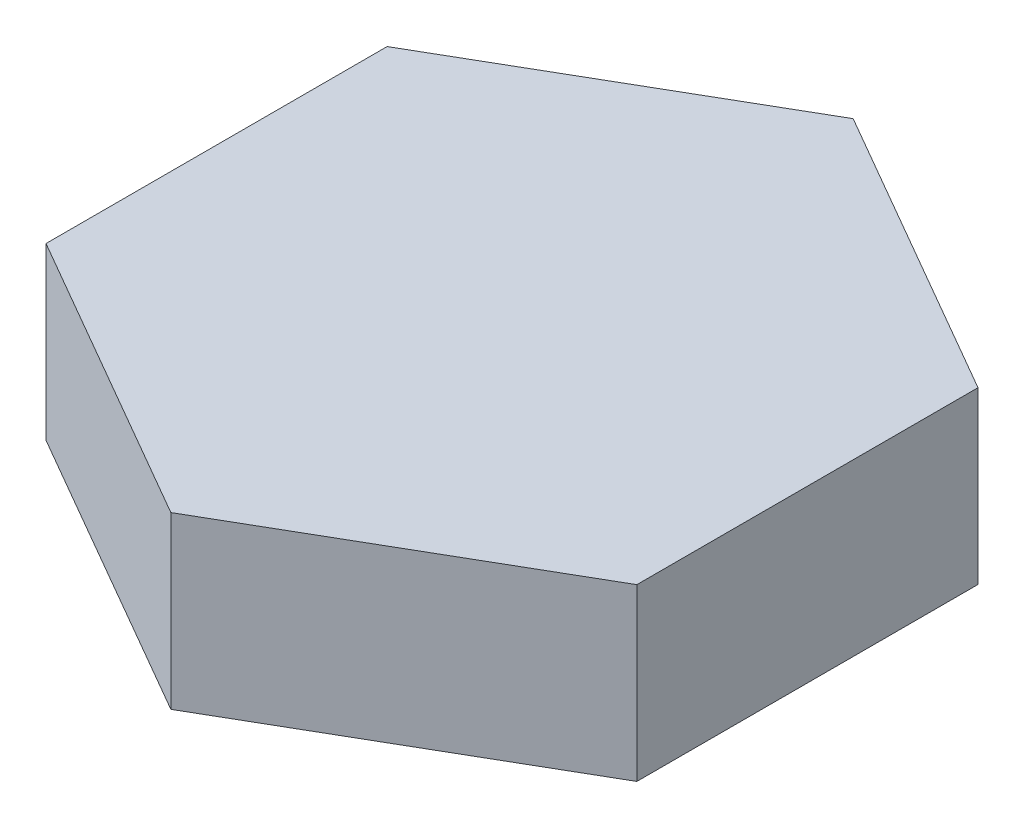
SolidWorks part; units mm, degrees
ref_plane "Front Plane" through (0, 0, 0) normal (0, 0, 1) x (1, 0, 0)
ref_plane "Top Plane" through (0, 0, 0) normal (0, 1, 0) x (1, 0, 0)
ref_plane "Right Plane" through (0, 0, 0) normal (1, 0, 0) x (0, 0, -1)
sketch "TopPlaneBase" plane through (0, 0, 0) normal (0, 1, 0) x (1, 0, 0)
  line L1 (0, 270.1999) -> (-234, 135.1)
  line L2 (-234, 135.1) -> (-234, -135.1)
  line L3 (-234, -135.1) -> (0, -270.1999)
  line L4 (0, -270.1999) -> (234, -135.1)
  line L5 (234, -135.1) -> (234, 135.1)
  line L6 (234, 135.1) -> (0, 270.1999)
  circle A0 centre (0, 0) radius 234 construction
  dimension "D1" = 468
extrude "Boss-Extrude1" add sketch "TopPlaneBase" along normal blind 135
